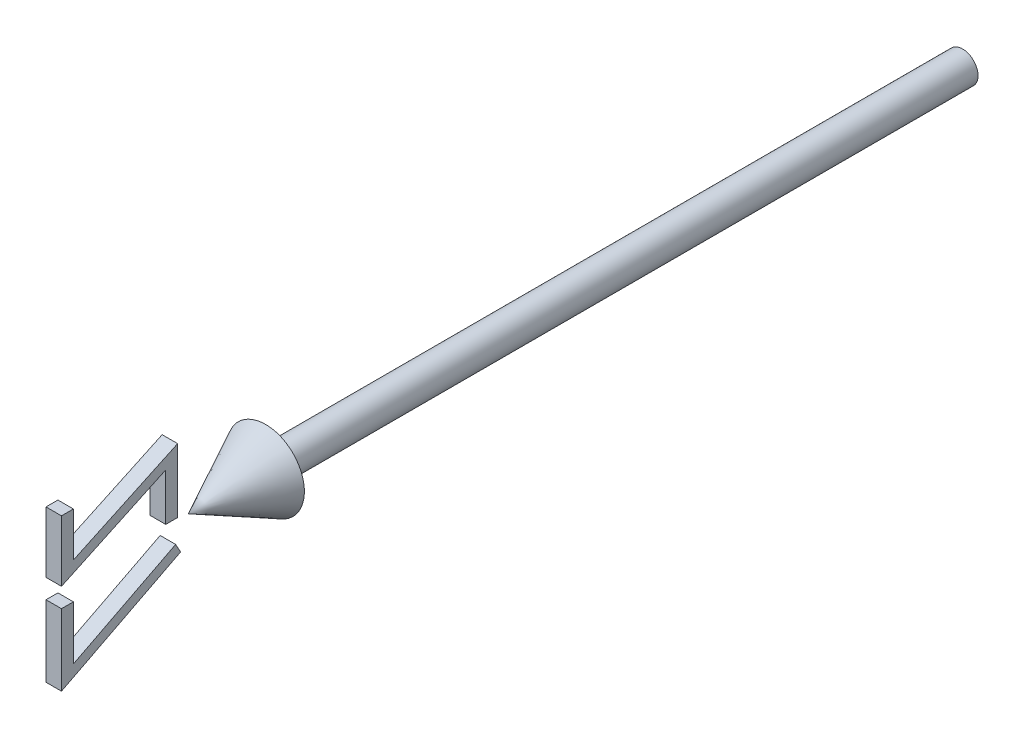
SolidWorks part; units mm, degrees
ref_plane "Front Plane" through (0, 0, 0) normal (0, 0, 1) x (1, 0, 0)
ref_plane "Top Plane" through (0, 0, 0) normal (0, 1, 0) x (1, 0, 0)
ref_plane "Right Plane" through (0, 0, 0) normal (1, 0, 0) x (0, 0, -1)
sketch "Sketch2" plane through (0, 0, 0) normal (0, 1, 0) x (1, 0, 0)
  line L0 (0, 41.95) -> (0, -114.4521) construction
  line L1 (-36.8894, 0) -> (41.4965, 0) construction
  line L2 (0, -100) -> (5, -90)
  line L3 (5, -90) -> (2, -90)
  line L4 (2, -90) -> (2, 0)
  line L5 (2, 0) -> (0, 0)
  line L6 (0, 0) -> (0, -100)
  dimension "D1" = 100
  dimension "D2" = 2
  dimension "D3" = 10
  dimension "D4" = 5
revolve "Revolve1" add sketch "Sketch2" angle 360 about L0
sketch "Sketch3" plane through (0, 0, 0) normal (1, 0, 0) x (0, -1, 0)
  line L0 (0, -101.5706) -> (0, -127.8138) construction
  line L1 (-10.1124, -102.3675) -> (14.1256, -102.3675) construction
  text T0 "Z7\r\n" font "Century Gothic" height 15
extrude "Boss-Extrude1" add sketch "Sketch3" against normal blind 1 and the other way blind 1 separate body
equation "\"frame_arrow_length\"=100"
equation "\"D1@Sketch2\"=\"frame_arrow_length\""
equation "\"frame_arrow_odA\"=4"
equation "\"D2@Sketch2\"=\"frame_arrow_odA\"/2"
equation "\"frame_arrow_head_od\"=5"
equation "\"D4@Sketch2\"=\"frame_arrow_head_od\""
equation "\"frame_arrow_head_length\"=10"
equation "\"D3@Sketch2\"=\"frame_arrow_head_length\""
equation "\"tvarobot_theta1\"=30"
equation "\"link0_ringA_odA\"= 40"
equation "\"link0_ringA_odB\"= 25"
equation "\"link0_ringA_id\"= 20"
equation "\"link0_ringA_thickness\"= (\"link0_ringA_odB\" - \"link0_ringA_id\")/2"
equation "\"link0_ringA_height\"= 3"
equation "\"link0_ringA_heightA\"= 1.5"
equation "\"link0_ringA_heightB\"=\"link0_ringA_height\"-\"link0_ringA_heightA\""
equation "\"link0_ringB_odA\"= 40"
equation "\"link0_ringB_odB\"= 29"
equation "\"link0_ringB_id\"= \"link0_shaftA_bearing_id\"+1"
equation "\"link0_ringB_thickness\"= (\"link0_ringB_odB\" - \"link0_ringB_id\")/2"
equation "\"link0_ringB_height\"= 3"
equation "\"link0_ringB_heightA\"= 1.5"
equation "\"link0_ringB_heightB\"=\"link0_ringB_height\"-\"link0_ringB_heightA\""
equation "\"link0_shaftA_bearing_od\"=27"
equation "\"link0_shaftA_bearing_id\"=20"
equation "\"link0_shaftA_thrust_bearing_od\"=35"
equation "\"link0_shaftA_thrust_bearing_id\"=20.04"
equation "\"link0_shaftA_retaining_ring_id\"=18.5"
equation "\"link0_shaftA_retaining_ring_groove_width\"=1.5"
equation "\"link0_shaftA_spline_length\"=8.0"
equation "\"link0_shaftA_spline_depth\"=1.0"
equation "\"link0_shaftA_spline_width\"=4.0"
equation "\"link0_shaftA_odA\"=\"link0_shaftA_bearing_id\""
equation "\"link0_shaftA_odB\"=35"
equation "\"link0_shaftA_odC\"=\"link0_shaftA_bearing_id\""
equation "\"link0_shaftA_odD\"=\"link0_shaftA_odC\"-2*\"link0_shaftA_spline_depth\""
equation "\"link0_shaftA_odE\"=\"link0_shaftA_bearing_id\""
equation "\"link0_shaftA_odF\"=\"link0_shaftA_odE\"-2*\"link0_shaftA_spline_depth\""
equation "\"link0_shaftA_idA\"=10"
equation "\"link0_shaftA_idB\"=6"
equation "\"link0_shaftA_length\"=39.5"
equation "\"link0_shaftA_lengthA\"=8.0"
equation "\"link0_shaftA_lengthB\"=12.0"
equation "\"link0_shaftA_lengthC\"=35.0"
equation "\"link0_shaftA_lengthD\"=39.0"
equation "\"link0_shaftA_lengthE\"=\"link0_shaftA_length\"-\"link0_shaftA_lengthD\""
equation "\"link0_shaftA_offsetX\"=11"
equation "\"link0_shaftA_offsetY\"=0"
equation "\"link0_shaftA_bolt_pattern_dia\"=14"
equation "\"link0_motor_center_dist\"=26"
equation "\"link0_46t_pulley_spline_length\"=8"
equation "\"link0_46t_pulley_spline_depth\"=\"link0_shaftA_spline_depth\"*1.025"
equation "\"link0_46t_pulley_spline_width\"=\"link0_shaftA_spline_width\"*1.05"
equation "\"link0_46t_pulley_idA\"=\"link0_shaftA_bearing_id\"*1.025"
equation "\"link0_46t_pulley_idB\"=\"link0_46t_pulley_idA\"-2*\"link0_46t_pulley_spline_depth\""
equation "\"link0_shaftB_spline_length\"=10"
equation "\"link0_shaftB_spline_depth\"=1.0"
equation "\"link0_shaftB_spline_width\"=1.25"
equation "\"link0_shaftB_length\"=7"
equation "\"link0_shaftB_lengthA\"=1.5"
equation "\"link0_shaftB_lengthB\"=2.75"
equation "\"link0_shaftB_odA\"=32"
equation "\"link0_shaftB_odB\"=22"
equation "\"link0_shaftB_odC\"=20"
equation "\"link0_shaftB_idA\"=10"
equation "\"link0_shaftB_bolt_diameter\"=19"
equation "\"link0_shaftB_bearing_od\"=27"
equation "\"link0_shaftB_bearing_id\"=20"
equation "\"link0_motor_length\"=46.5"
equation "\"link0_motor_width\"=28.5"
equation "\"link0_motor_height\"=34"
equation "\"link0_motor_offset\"=8"
equation "\"link0_shellA_thickness\"=2.5"
equation "\"link0_shellB_thickness\"=\"link0_shellA_thickness\""
equation "\"link0_plateA_shellA_height\"=48"
equation "\"link0_shellA_width\" =\"link0_plateA_width\""
equation "\"link0_shellA_height\" = \"link0_plateA_shellA_height\"-\"link0_plateA_height\""
equation "\"link0_shellA_length\" = \"link0_plateA_lengthB\" "
equation "\"link0_shellB_length\"=\"link0_shellA_length\""
equation "\"link0_shellA_radius\" = 0.375*25.4"
equation "\"link0_shellA_radiusA\"= \"link0_plateA_radiusA\""
equation "\"link0_shellA_radiusB\"= \"link0_plateA_radiusB\""
equation "\"link0_shellA_radiusC\"= 3"
equation "\"link0_postA_height\"=7"
equation "\"link0_postA_width\"=16"
equation "\"link0_postA_length\"=20"
equation "\"link0_postA_posX\"=22"
equation "\"link0_postA_posY\"=17.5"
equation "\"link0_postA_pocket_width\"=6.0"
equation "\"link0_postA_pocket_length\"=2.5"
equation "\"link0_postA_pocket_depth\"=9"
equation "\"link0_postA_pocket_posZ\"=10"
equation "\"link0_postB_height\"=7"
equation "\"link0_postB_width\"=16"
equation "\"link0_postB_length\"=20"
equation "\"link0_postB_posX\"=22"
equation "\"link0_postB_posY\"=17.5"
equation "\"link0_postB_id\"=3.0"
equation "\"link0_postB_pocket_width\"=6.0"
equation "\"link0_postB_pocket_length\"=2.5"
equation "\"link0_postB_pocket_depth\"=9"
equation "\"link0_postB_pocket_posZ\"=10"
equation "\"link0_postC_height\"=7"
equation "\"link0_postC_width\"=16"
equation "\"link0_postC_length\"=20"
equation "\"link0_postC_posX\"=22"
equation "\"link0_postC_posY\"=17.5"
equation "\"link0_postC_id\"=3.0"
equation "\"link0_postC_pocket_width\"=6.0"
equation "\"link0_postC_pocket_length\"=2.5"
equation "\"link0_postC_pocket_depth\"=9"
equation "\"link0_postC_pocket_posZ\"=10"
equation "\"link0_postD_height\"=7"
equation "\"link0_postD_width\"=16"
equation "\"link0_postD_length\"=20"
equation "\"link0_postD_posX\"=22"
equation "\"link0_postD_posY\"=17.5"
equation "\"link0_postD_id\"=3.0"
equation "\"link0_postD_pocket_width\"=6.0"
equation "\"link0_postD_pocket_length\"=3.0"
equation "\"link0_postD_pocket_depth\"=9"
equation "\"link0_postD_pocket_posZ\"=10"
equation "\"link0_postE_height\"=5"
equation "\"link0_postE_width\"=16"
equation "\"link0_postE_length\"=\"link0_plateE_lengthA\"-\"link0_lip_height\""
equation "\"link0_postE_posZ\"=22"
equation "\"link0_postE_posX\"=17.5"
equation "\"link0_postE_posY\"=22"
equation "\"link0_postE_id\"=3.0"
equation "\"link0_postE_cbore_id\"=6.5"
equation "\"link0_postE_hole_id\"=3"
equation "\"link0_postF_posZ\"=22"
equation "\"link0_postF_posX\"=17.5"
equation "\"link0_postF_posY\"=\"link0_plateB_lengthA\"+4"
equation "\"link0_postF_id\"=3.0"
equation "\"link0_postF_cbore_id\"=6.5"
equation "\"link0_postF_hole_id\"=3"
equation "\"link0_postG_posZ\"=22"
equation "\"link0_postG_posX\"=17.5"
equation "\"link0_postG_posY\"=\"link0_plateB_lengthA\"+12"
equation "\"link0_postG_id\"=3.0"
equation "\"link0_postG_cbore_id\"=6.5"
equation "\"link0_postG_hole_id\"=3"
equation "\"link0_postHIJ_posY\"=6"
equation "\"link0_postH_posX\"=28"
equation "\"link0_postH_posY\"=20"
equation "\"link0_postH_posZ\"=20"
equation "\"link0_postH_length\"=10"
equation "\"link0_postI_posX\"=28"
equation "\"link0_postI_posY\"=20"
equation "\"link0_postI_posZ\"=135"
equation "\"link0_postI_length\"=10"
equation "\"link0_postJ_posX\"=28"
equation "\"link0_postJ_posY\"=20"
equation "\"link0_postJ_posZ\"=175"
equation "\"link0_postJ_length\"=10"
equation "\"link0_postK_posX\"=28"
equation "\"link0_postK_posY\"=20"
equation "\"link0_postK_posZ\"=175"
equation "\"link0_postK_length\"=10"
equation "\"link0_postL_posX\"=28"
equation "\"link0_postL_posY\"=20"
equation "\"link0_postL_posZ\"=135"
equation "\"link0_postL_length\"=10"
equation "\"link0_postM_posX\"=28"
equation "\"link0_postM_posY\"=20"
equation "\"link0_postM_posZ\"=35"
equation "\"link0_postM_length\"=10"
equation "\"link0_plateA_lengthA\"=30"
equation "\"link0_plateA_lengthB\"=150"
equation "\"link0_plateA_lengthC\"=30"
equation "\"link0_plateA_length\"=\"link0_plateA_lengthA\"+\"link0_plateA_lengthB\"+\"link0_plateA_lengthC\""
equation "\"link0_plateA_width\"=  68"
equation "\"link0_plateA_height\"= \"link0_plateA_radiusA\""
equation "\"link0_plateA_thickness\"=\"link0_shellA_thickness\""
equation "\"link0_plateA_radius\"= 9.5"
equation "\"link0_plateA_radiusA\"= 18"
equation "\"link0_plateA_radiusB\"= 18"
equation "\"link0_plateA_radiusC\"= 3"
equation "\"link0_plateB_length\"= 40"
equation "\"link0_plateB_width\"= \"link0_plateA_width\"*1.005"
equation "\"link0_plateB_height\"= \"link0_plateA_shellA_height\"*1.005"
equation "\"link0_plateB_lengthA\"=\"link0_lip_height\"+\"link0_plateD_thickness\"+\"link0_motor_mount_thickness\""
equation "\"link0_plateB_lengthB\"=\"link0_plateB_height\"-\"link0_plateB_lengthA\""
equation "\"link0_plateB_radiusA\"= \"link0_plateA_radiusA\""
equation "\"link0_plateB_radiusB\"= \"link0_plateA_radiusB\""
equation "\"link0_plateB_radiusC\"= 3"
equation "\"link0_plateB_idA\"=\"link0_shaftA_odC\"+1"
equation "\"link0_plateB_idB\"=\"link0_shaftA_bearing_od\"-2"
equation "\"link0_plateB_idC\"=\"link0_shaftA_bearing_od\"*1.005"
equation "\"link0_plateB_idD\"=\"link0_shaftA_thrust_bearing_od\"+1 "
equation "\"link0_plateB_depthA\"=1.0"
equation "\"link0_plateB_depthB\"=2.0"
equation "\"link0_plateB_depthC\"=8"
equation "\"link0_plateB_depthD\"=\"link0_plateB_length\"-\"link0_lip_height\"-\"link0_plateD_thickness\" "
equation "\"link0_plateC_length\"=\"link0_plateB_length\""
equation "\"link0_plateC_width\"= \"link0_plateB_width\""
equation "\"link0_plateC_height\"= .1*25.4"
equation "\"link0_plateA_hole_od\" = 0.1*25.4"
equation "\"link0_plateA_hole_delx\" = 0.5*25.4"
equation "\"link0_plateA_hole_delz\" = 0.75*25.4"
equation "\"link0_plateA_hole_offx\" = 0.0*25.4"
equation "\"link0_plateA_hole_offz\" = \"link0_plateA_length\"/2"
equation "\"link0_plateB_hole_od\" = 0.1*25.4"
equation "\"link0_plateB_hole_delx\"= 0.75*25.4"
equation "\"link0_plateB_hole_delz\"= 0.75*25.4"
equation "\"link0_plateB_hole_offx\"= 0.0*25.4"
equation "\"link0_plateB_hole_offz\"= 0.0*25.4"
equation "\"link0_plateC_hole_od\"= 0.1*25.4"
equation "\"link0_plateC_hole_delx\"= 0.75*25.4"
equation "\"link0_plateC_hole_delz\"= 0.75*25.4"
equation "\"link0_plateC_hole_offx\"= 0.0*25.4"
equation "\"link0_plateC_hole_offz\"= 0.0*25.4"
equation "\"link0_plateD_height\"=\"link0_plateB_height\"-2*\"link0_shellA_thickness\""
equation "\"link0_plateD_width\"=\"link0_plateB_width\"-2*\"link0_shellA_thickness\""
equation "\"link0_plateD_thickness\"=10"
equation "\"link0_plateD_radiusA\"=\"link0_plateB_radiusA\"-\"link0_shellA_thickness\""
equation "\"link0_plateD_odA\"= .375*25.4"
equation "\"link0_plateD_odB\"= .375*25.4"
equation "\"link0_plateD_bearing_id\"=20"
equation "\"link0_plateD_bearing_od\"=27"
equation "\"link0_plateE_radiusA\"=\"link0_plateA_radiusA\""
equation "\"link0_plateE_radiusB\"=\"link0_plateA_radiusB\""
equation "\"link0_plateE_radiusC\"=8.0"
equation "\"link0_plateE_length\"=30"
equation "\"link0_plateE_lengthA\"=16"
equation "\"link0_plateE_height\"=\"link0_plateB_height\""
equation "\"link0_plateE_width\"=\"link0_plateB_width\""
equation "\"link0_plateE_odA\"=\"gantry_coupler_id\"*0.99"
equation "\"link0_plateE_idA\"=\"link0_plateE_odA\"-20.0"
equation "\"link0_plateE_spline_depth\"=\"link0_poleA_spline_depth\"*1.05"
equation "\"link0_plateE_spline_width\"=\"link0_poleA_spline_width\"*1.075"
equation "\"link0_plateE_spline_length\"=\"link0_poleA_spline_length\""
equation "\"link0_plateE_coupler_length\"=46"
equation "\"link0_lip_height\"=5.0"
equation "\"link0_lip_thickness\"=2.0"
equation "\"link0_motor_mount_thickness\"=8.0"
equation "\"link0_motor_mount_idA\"=22"
equation "\"link0_motor_mount_idB\"=\"link0_shaftB_bearing_od\"*1.005"
equation "\"link0_motor_mount_idC\"=\"link0_shaftB_bearing_od\"-2"
equation "\"link0_motor_mount_depthA\"=5.5"
equation "\"link0_motor_mount_height\"=\"link0_plateD_height\""
equation "\"link0_motor_mount_width\"=\"link0_plateD_width\""
equation "\"link0_motor_mountL_height\"=36"
equation "\"link0_motor_mountL_heightA\"=12"
equation "\"link0_motor_mountL_length\"=50"
equation "\"link0_motor_mountL_lengthA\"=36"
equation "\"gantry_coupler_od\"=25.4*2.0"
equation "\"gantry_coupler_id\"=1.645*25.4"
equation "\"gantry_coupler_offsetX\"=\"link0_plateE_width\"/2"
equation "\"link0_poleA_odA\"=20"
equation "\"link0_poleA_odB\"=36"
equation "\"link0_poleA_idA\"=\"link0_poleA_odA\"-2*\"link0_poleA_thickness\""
equation "\"link0_poleA_idB\"=(\"link0_plateE_idA\"/2+1.5*\"link0_lip_thickness\")*1.04"
equation "\"link0_poleA_thickness\"=3.5"
equation "\"link0_poleA_length\"=100"
equation "\"link0_poleA_lengthA\"=18.5"
equation "\"link0_poleA_lengthB\"=80"
equation "\"link0_poleA_gasket_thickness\"=1.5"
equation "\"link0_poleA_spline_depth\"=1.0"
equation "\"link0_poleA_spline_width\"=4.0"
equation "\"link0_poleA_spline_length\"=10.0"
equation "\"link1_plateB_length\"=30"
equation "\"link1_lip_height\"=\"link0_lip_height\""
equation "\"link0_tension_plateA_width\"=12"
equation "\"link0_tension_plateA_lengthA\"=10.5"
equation "\"link0_tension_plateB_width\"=\"link0_tension_plateA_width\""
equation "\"link0_tension_plateB_lengthA\"=\"link0_tension_plateA_lengthA\""
equation "\"link0_tension_wheelA_posZ\"=7"
equation "\"link0_tension_wheelA_posX\"=\"link0_plateD_height\"/2-\"link0_tension_plateA_lengthA\""
equation "\"link0_m2_clear_hole_id\"=2.35"
equation "\"link0_m2_insert_hole_id\"=2.5"
equation "\"link0_m2_tap_hole_id\"=1.75"
equation "\"link0_m2_nut_socket_width\"=4.25"
equation "\"link0_m2_nut_socket_depth\"=2.5"
equation "\"link0_m2_cbore_id\"=3.75"
equation "\"link0_m2_cbore_depth\"=7"
equation "\"link0_m2_5_clear_hole_id\"=2.75"
equation "\"link0_m2_5_insert_hole_id\"=2.75"
equation "\"link0_m2_5_tap_hole_id\"=2.25"
equation "\"link0_m2_5_nut_socket_width\"=5.25"
equation "\"link0_m2_5_nut_socket_depth\"=2.5"
equation "\"link0_m2_5_cbore_id\"=4.75"
equation "\"link0_m2_5_cbore_depth\"=2.5"
equation "\"link0_m2_5_insert_access_length\"=6.0"
equation "\"link0_m2_5_insert_access_width\"=3.0"
equation "\"link0_m3_clear_hole_id\"=3.25"
equation "\"link0_m3_insert_hole_id\"=3"
equation "\"link0_m3_tap_hole_id\"=2.75"
equation "\"link0_m3_nut_socket_width\"=5.75"
equation "\"link0_m3_nut_socket_depth\"=4.0"
equation "\"link0_m3_cbore_id\"=5.75"
equation "\"link0_m3_cbore_depth\"=3.5"
equation "\"link0_m3_insert_access_length\"=4.5"
equation "\"link0_m3_insert_access_width\"=3.5"
equation "\"link0_rpi_mount_height\"=6"
equation "\"link0_rpi_mount_width\"=49"
equation "\"link0_rpi_mount_length\"=58"
equation "\"link0_rpi_mount_post_od\"=6"
equation "\"link0_rpi_mount_posZ\"=72"
equation "\"link0_rpi_mount_posX\"=11.5"
equation "\"link0_mcu_mount_height\"=5"
equation "\"link0_mcu_mount_width\"=49"
equation "\"link0_mcu_mount_length\"=58"
equation "\"link0_mcu_mount_post_od\"=6"
equation "\"link0_mcu_mount_posZ\"=164"
equation "\"link0_mcu_mount_posX\"=4"
equation "\"link0_pwr_mount_height\"=4"
equation "\"link0_pwr_mount_width\"=15.75"
equation "\"link0_pwr_mount_length\"=75.75"
equation "\"link0_pwr_mount_post_od\"=6"
equation "\"link0_pwr_mount_posZ\"=75"
equation "\"link0_pwr_mount_posX\"=16"
equation "\"link0_pwr_board_height\"=6"
equation "\"link0_pwr_board_width\"=21"
equation "\"link0_pwr_board_length\"=80"
